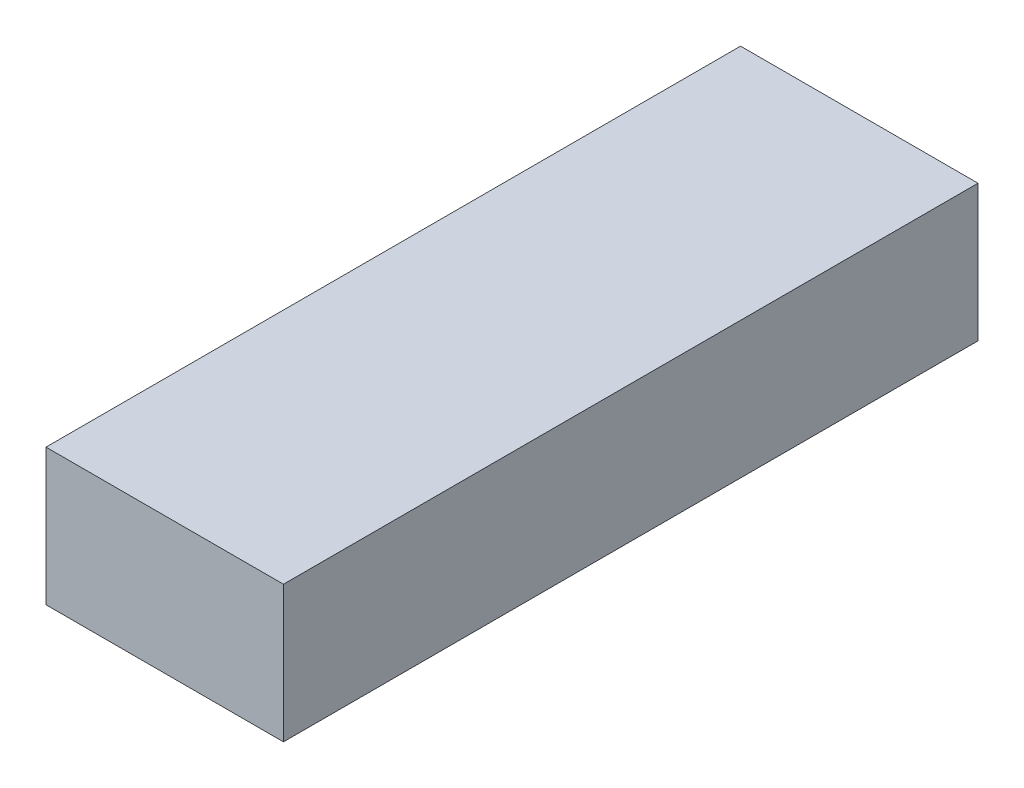
SolidWorks part; units mm, degrees
ref_plane "Plan de face" through (0, 0, 0) normal (0, 0, 1) x (1, 0, 0)
ref_plane "Plan de dessus" through (0, 0, 0) normal (0, 1, 0) x (1, 0, 0)
ref_plane "Plan de droite" through (0, 0, 0) normal (1, 0, 0) x (0, 0, -1)
sketch "Esquisse1" plane through (0, 0, 0) normal (0, 0, 1) x (1, 0, 0)
  line L1 (0, 0) -> (40, 0)
  line L2 (0, 0) -> (0, 23)
  line L3 (0, 23) -> (40, 23)
  line L4 (40, 0) -> (40, 23)
  dimension "D1" = 40
  dimension "D2" = 23
extrude "Boss.-Extru.1" add sketch "Esquisse1" along normal blind 117
